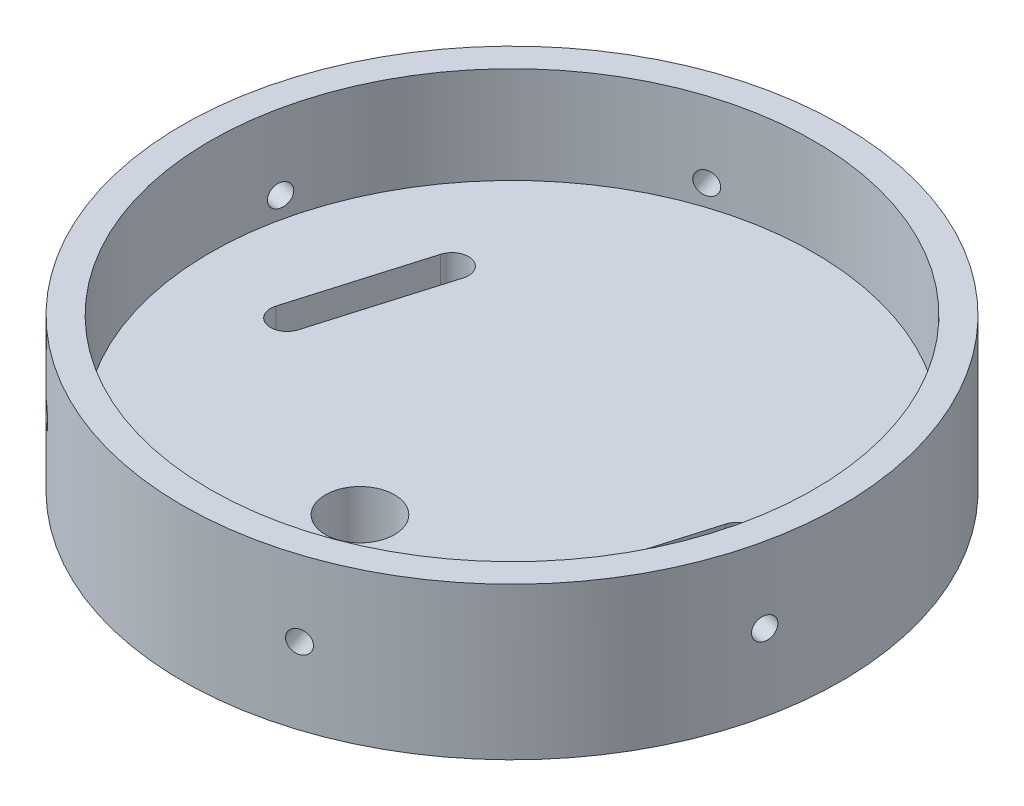
SolidWorks part; units mm, degrees
material "6061-T4 (SS)"
ref_plane "Front Plane" through (0, 0, 0) normal (0, 0, 1) x (1, 0, 0)
ref_plane "Top Plane" through (0, 0, 0) normal (0, 1, 0) x (1, 0, 0)
ref_plane "Right Plane" through (0, 0, 0) normal (1, 0, 0) x (0, 0, -1)
sketch "Sketch1" plane through (0, 0, 0) normal (0, 1, 0) x (1, 0, 0)
  circle A0 centre (0, 0) radius 75.692
  circle A1 centre (0, 0) radius 69.342
  dimension "D1" = 151.384
  dimension "D2" = 138.684
extrude "Boss-Extrude1" add sketch "Sketch1" along normal blind 22.225
sketch "Sketch2" plane through (0, 0, 0) normal (0, -1, 0) x (1, 0, 0)
  circle A0 centre (0, 0) radius 75.692
  dimension "D1" = 151.384
extrude "Boss-Extrude2" add sketch "Sketch2" along normal blind 12.7
hole_wizard "Tap Drill for 1/4-20 Tap1" positions "3DSketch2" profile "Sketch4" hole size "1/4-20" standard "ANSI Inch"
sketch3d "3DSketch2"
  line L0 (73.6526, 22.225, 17.4519) -> (73.9972, 4.8963, 15.9279)
  circle A1 centre (0, 22.225, 0) radius 75.692 construction
  point P0 (73.9972, 4.8963, 15.9279)
  point P10 (0, 97.917, 0)
  point P12 (-133.403, 50.4262, 0)
  dimension "D1" = 17.399
sketch "Sketch4" plane through (73.9972, 4.8963, 15.9279) normal (0, 1, 0) x (0.2104, 0, -0.9776)
  line L0 (0, 0) -> (0, 11.1858)
  line L1 (0, 11.1858) -> (2.5527, 9.652)
  line L2 (2.5527, 9.652) -> (2.5527, 0)
  line L5 (2.5527, 0) -> (0, 0)
  line L10 (0, 11.1858) -> (-2.5527, 9.652) construction
  line L11 (0, -6.35) -> (0, 107.95) construction
  dimension "Hole Dia." = 5.1054
  dimension "Hole Depth" = 9.652
  dimension "Drill Angle" = 118
pattern_circular "CirPattern1" count 6 over 360 about axis through (0, 22.225, 0) along (0, -1, 0) of "Tap Drill for 1/4-20 Tap1" reverse direction yes
sketch "Sketch5" plane through (0, 0, 0) normal (0, 1, 0) x (1, 0, 0)
  circle A2 centre (0, 0) radius 44.45 construction
  point P0 (0, -34.925)
  point P1 (-43.1997, 10.4686)
  point P3 (43.1997, -10.4686)
  point P4 (0, 0)
  dimension "D2" = 88.9
  dimension "D1" = 34.925
  dimension "D3" = 88.9
hole_wizard "5/8 (0.625) Diameter Hole1" positions "Sketch6" profile "Sketch8" hole size "5/8" standard "ANSI Inch" end condition through all
sketch "Sketch6" plane through (0, 0, 0) normal (0, 1, 0) x (1, 0, 0)
  point P0 (0, -34.925)
  point P4 (0, -29.3768)
sketch "Sketch8" plane through (0, 0, 34.925) normal (1, 0, 0) x (0, 0, 1)
  line L0 (0, 0) -> (0, 12.7)
  line L1 (0, 12.7) -> (7.9375, 12.7)
  line L2 (7.9375, 12.7) -> (7.9375, 0)
  line L5 (7.9375, 0) -> (0, 0)
  line L11 (0, -6.35) -> (0, 107.95) construction
  dimension "Thru Hole Dia." = 15.875
  dimension "Thru Hole Depth" = 12.7
sketch "Sketch11" plane through (0, 0, 0) normal (0, 1, 0) x (1, 0, 0)
  line L0 (-47.5107, -4.1489) -> (-38.8886, 25.0862) construction
  line L1 (-51.1651, -3.0712) -> (-42.543, 26.1639)
  line L2 (-43.8563, -5.2267) -> (-35.2343, 24.0084)
  line L3 (38.8886, -25.0862) -> (47.5107, 4.1489) construction
  line L4 (35.2343, -24.0084) -> (43.8563, 5.2267)
  line L5 (42.543, -26.1639) -> (51.1651, 3.0712)
  arc A0 (-51.1651, -3.0712) -> (-43.8563, -5.2267) centre (-47.5107, -4.1489) ccw
  arc A1 (-35.2343, 24.0084) -> (-42.543, 26.1639) centre (-38.8886, 25.0862) ccw
  arc A2 (35.2343, -24.0084) -> (42.543, -26.1639) centre (38.8886, -25.0862) ccw
  arc A3 (51.1651, 3.0712) -> (43.8563, 5.2267) centre (47.5107, 4.1489) ccw
  point P2 (-43.1997, 10.4686)
  point P9 (43.1997, -10.4686)
  dimension "D1" = 3.81
  dimension "D4" = 3.81
  dimension "D2" = 30.48
  dimension "D3" = 30.48
extrude "Cut-Extrude1" cut sketch "Sketch11" against normal through all
